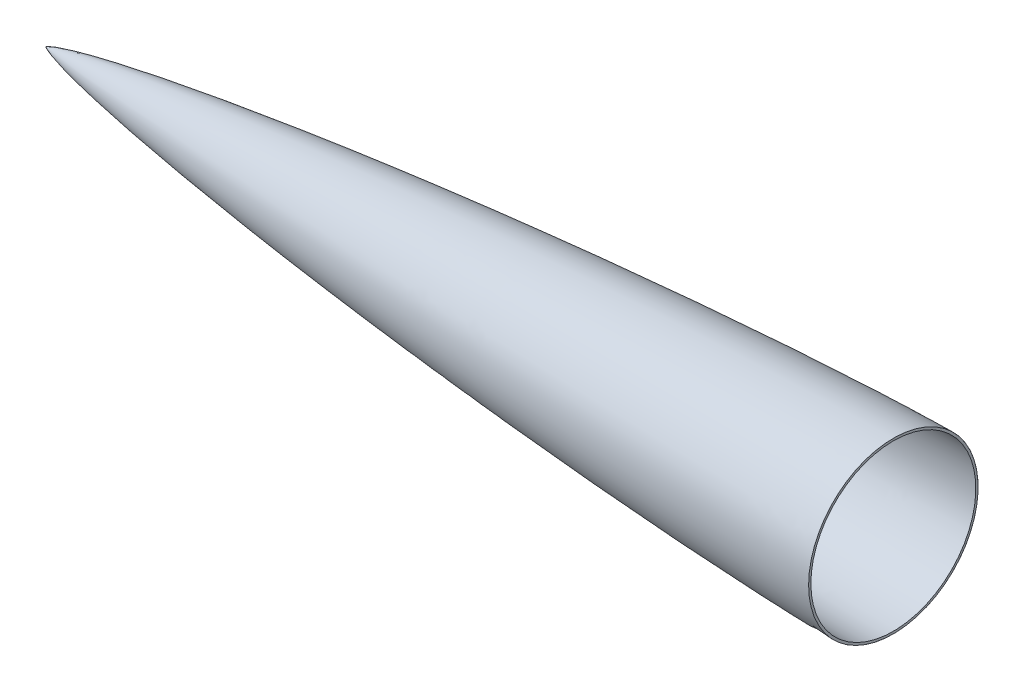
SolidWorks part; units mm, degrees
material "Fibra di Carbonio"
ref_plane "Front Plane" through (0, 0, 0) normal (0, 0, 1) x (1, 0, 0)
ref_plane "Top Plane" through (0, 0, 0) normal (0, 1, 0) x (1, 0, 0)
ref_plane "Right Plane" through (0, 0, 0) normal (1, 0, 0) x (0, 0, -1)
sketch "Sketch2" plane through (0, 0, 0) normal (0, 0, 1) x (1, 0, 0)
  line L0 (0, 0) -> (750, 0) construction
  line L1 (750, 75) -> (750, 0) construction
  line L2 (0, 0) -> (4.5526, 0)
  line L3 (750, 75) -> (750.005, 73)
  line L4 (4.5526, 0) -> (18.241, -6.6941) construction
  line L5 (0, 0) -> (17.3624, -8.4908) construction
  line L6 (750.005, 73) -> (750.005, 75)
  line L7 (750, 75) -> (750.005, 75)
  spline S0 degree 4 poles (0, 0) (0.0027, 0.0074) (0.0091, 0.0215) (0.0269, 0.047) (0.0684, 0.0933) (0.1314, 0.151) (0.2168, 0.2183) (0.3382, 0.3041) (0.4839, 0.3974) (0.6551, 0.4981) (0.8516, 0.6056) (1.1377, 0.7534) (1.5815, 0.9661) (2.3351, 1.2961) (3.6829, 1.8266) (6.1115, 2.6745) (10.5746, 4.038) (18.9517, 6.252) (33.5701, 9.5653) (58.4067, 14.4079) (92.5079, 20.1209) (133.842, 26.2251) (179.8092, 32.3065) (225.8421, 37.8632) (271.9254, 42.9839) (318.0491, 47.7253) (364.2071, 52.1207) (410.3947, 56.191) (456.6091, 59.9459) (502.848, 63.3865) (549.1098, 66.5042) (595.3934, 69.2798) (635.9102, 71.3773) (670.652, 72.8985) (698.6683, 73.9066) (717.5285, 74.458) (733.0226, 74.8041) (742.7236, 74.948) (747.5745, 74.994) (750, 75) knots 0 0 0 0 0 0.000041 0.000082 0.000164 0.000329 0.000493 0.000658 0.000951 0.001245 0.001545 0.001844 0.002657 0.003853 0.005902 0.009516 0.016281 0.028569 0.051794 0.088907 0.150314 0.211721 0.273128 0.334535 0.395942 0.457348 0.518755 0.580162 0.641569 0.702976 0.764383 0.825789 0.887196 0.9179 0.948603 0.974302 0.987151 1 1 1 1 1 construction
  spline S1 degree 4 poles (0, 0) (0.0027, 0.0074) (0.0091, 0.0215) (0.0269, 0.047) (0.0684, 0.0933) (0.1314, 0.151) (0.2168, 0.2183) (0.3382, 0.3041) (0.4839, 0.3974) (0.6551, 0.4981) (0.8516, 0.6056) (1.1377, 0.7534) (1.5815, 0.9661) (2.3351, 1.2961) (3.6829, 1.8266) (6.1115, 2.6745) (10.5746, 4.038) (18.9517, 6.252) (33.5701, 9.5653) (58.4067, 14.4079) (92.5079, 20.1209) (133.842, 26.2251) (179.8092, 32.3065) (225.8421, 37.8632) (271.9254, 42.9839) (318.0491, 47.7253) (364.2071, 52.1207) (410.3947, 56.191) (456.6091, 59.9459) (502.848, 63.3865) (549.1098, 66.5042) (595.3934, 69.2798) (635.9102, 71.3773) (670.652, 72.8985) (698.6683, 73.9066) (717.5285, 74.458) (733.0226, 74.8041) (742.7236, 74.948) (747.5745, 74.994) (750, 75) knots 0 0 0 0 0 0.000041 0.000082 0.000164 0.000329 0.000493 0.000658 0.000951 0.001245 0.001545 0.001844 0.002657 0.003853 0.005902 0.009516 0.016281 0.028569 0.051794 0.088907 0.150314 0.211721 0.273128 0.334535 0.395942 0.457348 0.518755 0.580162 0.641569 0.702976 0.764383 0.825789 0.887196 0.9179 0.948603 0.974302 0.987151 1 1 1 1 1
  spline S2 degree 1 poles (4.5526, 0) (750.005, 73) knots 0 0 1 1 construction
  spline S3 degree 3 poles (4.5526, 0) (5.445, 0.3249) (7.239, 0.923) (10.9289, 2.0351) (17.4708, 3.796) (26.9445, 6.0175) (38.3871, 8.4241) (53.7067, 11.3983) (72.9318, 14.7925) (96.0679, 18.5265) (119.2498, 22.0067) (150.2024, 26.3764) (188.9573, 31.415) (235.5315, 36.9454) (282.158, 42.0423) (328.826, 46.7595) (391.0967, 52.5838) (469.0103, 59.0427) (547.0044, 64.4339) (609.4413, 68.0319) (656.2876, 70.325) (695.3421, 71.8297) (722.6802, 72.5863) (738.3058, 72.8883) (746.1038, 72.9903) (750.005, 73) knots 0.005737 0.005737 0.005737 0.005737 0.00962 0.013504 0.021272 0.036807 0.052343 0.067878 0.098949 0.130019 0.16109 0.192161 0.254302 0.316444 0.378585 0.440727 0.502868 0.627151 0.751434 0.813576 0.875717 0.937859 0.968929 0.984465 1 1 1 1
  dimension "D1" = 75
  dimension "D2" = 750
  dimension "D3" = 2
revolve "Revolve1" add sketch "Sketch2" angle 360 about L0 region at (373.2656, 52.1198, 0) region at (750.0033, 74.3333, 0)
